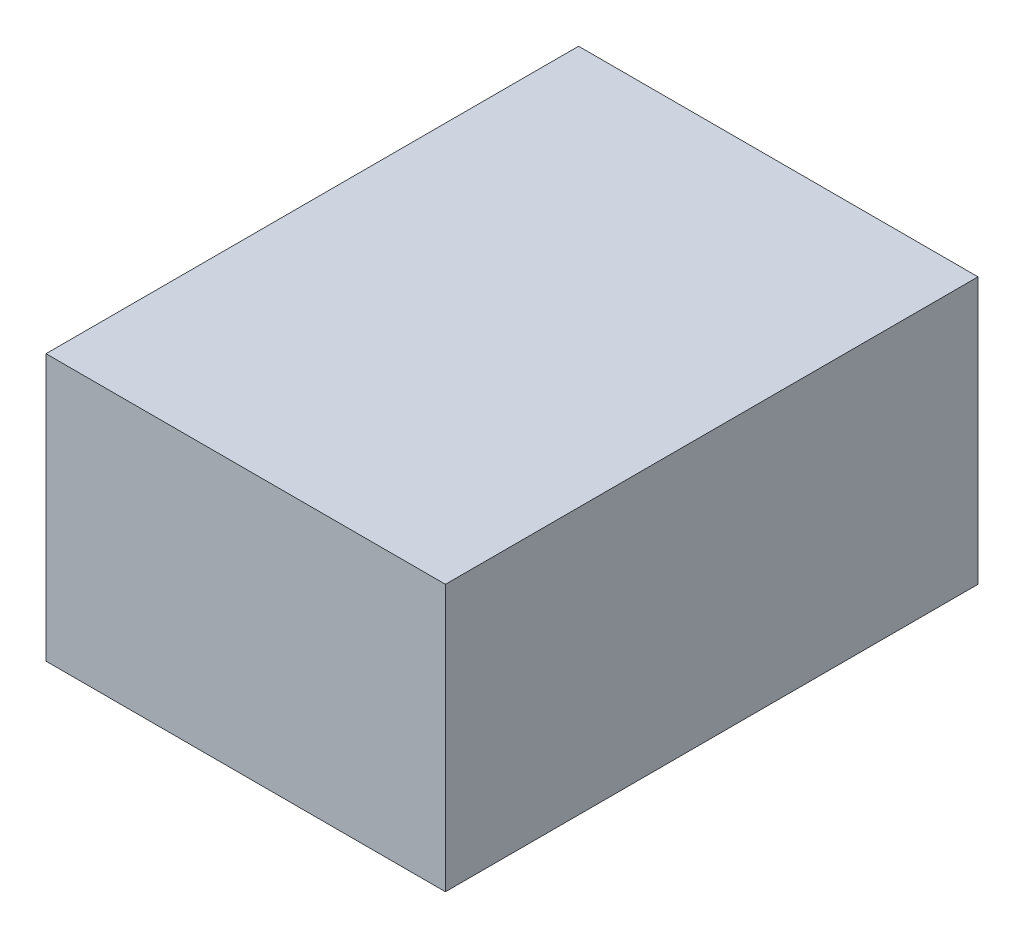
SolidWorks part; units mm, degrees
ref_plane "前视基准面" through (0, 0, 0) normal (0, 0, 1) x (1, 0, 0)
ref_plane "上视基准面" through (0, 0, 0) normal (0, 1, 0) x (1, 0, 0)
ref_plane "右视基准面" through (0, 0, 0) normal (1, 0, 0) x (0, 0, -1)
other "Configuration Table"
sketch "草图1" plane through (0, 0, 0) normal (0, 1, 0) x (1, 0, 0)
  line L1 (-30, -40) -> (30, -40)
  line L2 (-30, -40) -> (-30, 40)
  line L3 (-30, 40) -> (30, 40)
  line L4 (30, -40) -> (30, 40)
  line L5 (-30, -40) -> (30, 40) construction
  line L6 (-30, 40) -> (30, -40) construction
  point P0 (0, 0)
extrude "凸台-拉伸1" add sketch "草图1" along normal blind 40
